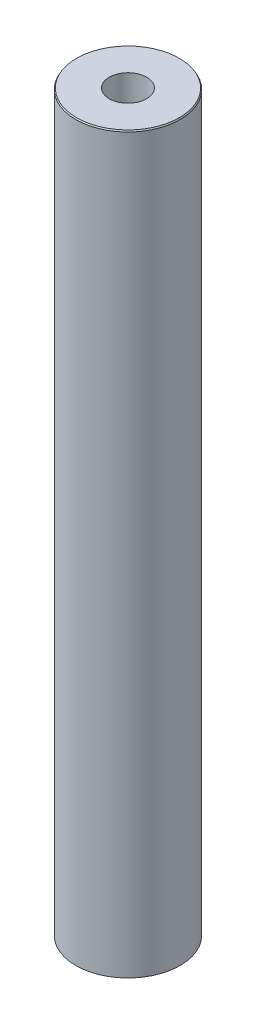
SolidWorks part; units mm, degrees
ref_plane "Front Plane" through (0, 0, 0) normal (0, 0, 1) x (1, 0, 0)
ref_plane "Top Plane" through (0, 0, 0) normal (0, 1, 0) x (1, 0, 0)
ref_plane "Right Plane" through (0, 0, 0) normal (1, 0, 0) x (0, 0, -1)
sketch "Sketch1" plane through (0, 0, 0) normal (0, 1, 0) x (1, 0, 0)
  circle A0 centre (0, 0) radius 42.5
  dimension "SHAFT_OD" = 85
extrude "Boss-Extrude1" add sketch "Sketch1" along normal blind 598.63
sketch "Sketch2" plane through (0, 0, 0) normal (0, 1, 0) x (1, 0, 0)
  circle A0 centre (0, 0) radius 15.2415
  dimension "BORE_D" = 30.483
extrude "Cut-Extrude1" cut sketch "Sketch2" along normal through all
chamfer "Chamfer1" distance 1.052 angle 30 2 edges at (0, 598.63, 42.5) (0, 0, 42.5) first distance on face at (0, 598.63, 42.5) first distance on face at (0, 0, 15.2415)
